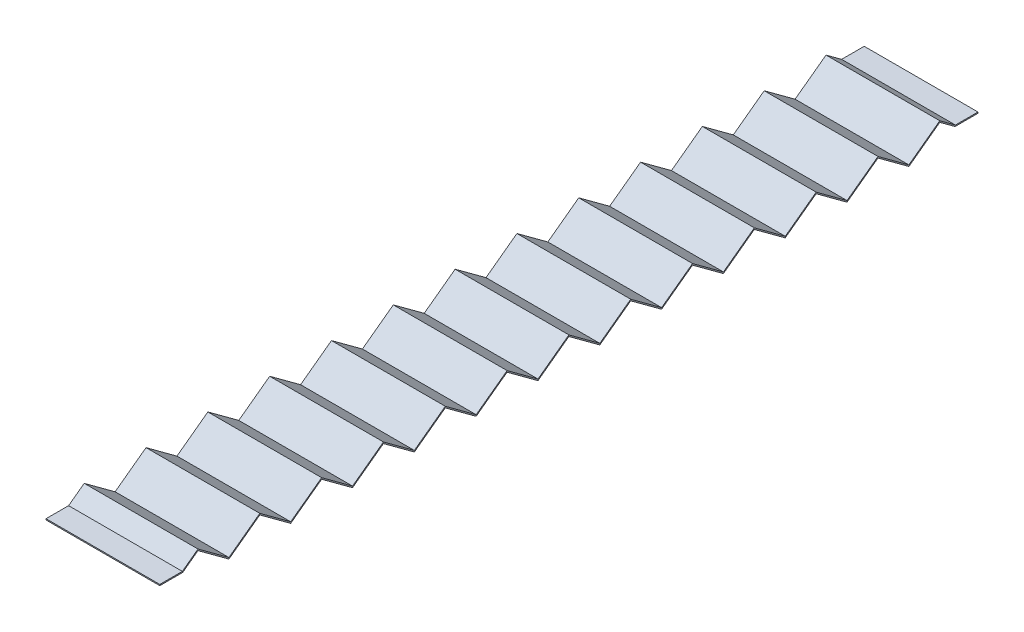
SolidWorks part; units mm, degrees
ref_plane "Front Plane" through (0, 0, 0) normal (0, 0, 1) x (1, 0, 0)
ref_plane "Top Plane" through (0, 0, 0) normal (0, 1, 0) x (1, 0, 0)
ref_plane "Right Plane" through (0, 0, 0) normal (1, 0, 0) x (0, 0, -1)
sketch "Sketch2" plane through (0, 0, 0) normal (0, 0, 1) x (1, 0, 0)
  line L1 (-27.5, 10) -> (27.5, 10)
  line L2 (-27.5, 10) -> (-27.5, 0)
  line L3 (-27.5, 0) -> (27.5, 0)
  line L4 (27.5, 10) -> (27.5, 0)
  point P4 (0, 0)
  dimension "D1" = 10
  dimension "D2" = 55
sketch "Sketch3" plane through (0, 0, 0) normal (1, 0, 0) x (0, 0, -1)
  line L0 (0, 10) -> (359.5261, 10) construction
  line L1 (0, 0) -> (359.5261, 0) construction
  line L3 (10, 5) -> (16.7905, 10)
  line L4 (16.7905, 10) -> (30.3716, 0)
  line L5 (30.3716, 0) -> (43.9526, 10)
  line L6 (43.9526, 10) -> (57.5336, 0)
  line L7 (57.5336, 0) -> (71.1147, 10)
  line L8 (71.1147, 10) -> (84.6957, 0)
  line L9 (84.6957, 0) -> (98.2768, 10)
  line L10 (98.2768, 10) -> (111.8578, 0)
  line L11 (111.8578, 0) -> (125.4389, 10)
  line L12 (125.4389, 10) -> (139.0199, 0)
  line L13 (139.0199, 0) -> (152.6009, 10)
  line L14 (152.6009, 10) -> (166.182, 0)
  line L15 (166.182, 0) -> (179.763, 10)
  line L16 (179.763, 10) -> (193.3441, 0)
  line L17 (193.3441, 0) -> (206.9251, 10)
  line L18 (206.9251, 10) -> (220.5062, 0)
  line L19 (0, 10) -> (0, 0) construction
  line L20 (220.5062, 0) -> (234.0872, 10)
  line L21 (234.0872, 10) -> (247.6682, 0)
  line L22 (247.6682, 0) -> (261.2493, 10)
  line L23 (261.2493, 10) -> (274.8303, 0)
  line L24 (274.8303, 0) -> (288.4114, 10)
  line L25 (288.4114, 10) -> (301.9924, 0)
  line L26 (301.9924, 0) -> (315.5735, 10)
  line L27 (315.5735, 10) -> (329.1545, 0)
  line L28 (329.1545, 0) -> (342.7355, 10)
  line L29 (342.7355, 10) -> (349.5261, 5)
  line L30 (359.5261, 10) -> (359.5261, 0) construction
  line L31 (10, 5) -> (0, 5)
  line L32 (349.5261, 5) -> (359.5261, 5)
  line L33 (359.5261, -12.3958) -> (359.5261, -19.8536) construction
  dimension "D2" = 10
  dimension "D1" = 10
  dimension "D3" = 10
extrude "Extrude-Thin1" add sketch "Sketch3" against normal mid plane 50 thin thin type mid plane wall 0.5
